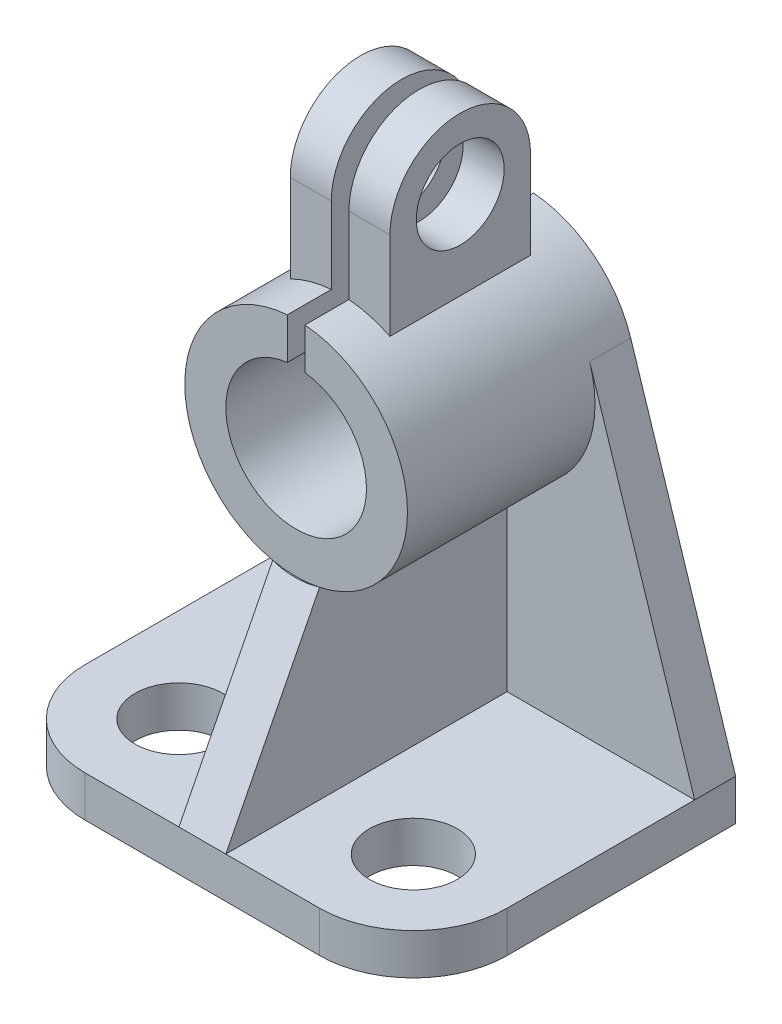
SolidWorks part; units mm, degrees
ref_plane "Front Plane" through (0, 0, 0) normal (0, 0, 1) x (1, 0, 0)
ref_plane "Top Plane" through (0, 0, 0) normal (0, 1, 0) x (1, 0, 0)
ref_plane "Right Plane" through (0, 0, 0) normal (1, 0, 0) x (0, 0, -1)
sketch "Sketch1" plane through (0, 0, 0) normal (0, 0, 1) x (1, 0, 0)
  line L0 (0, 0) -> (-33638.0787, 0) construction
  line L1 (0, 0) -> (0, 33638.0787) construction
  line L2 (-1.5, 68.9059) -> (-1.5, 75.9407)
  line L3 (36, 7) -> (-36, 7)
  line L4 (36, 7) -> (36, 0)
  line L5 (36, 0) -> (-36, 0)
  line L6 (-36, 7) -> (-36, 0)
  line L7 (0, 0) -> (0, 7) construction
  line L8 (36, 3.5) -> (-36, 3.5) construction
  line L9 (-4, 7) -> (4, 7)
  line L10 (-4, 7) -> (-4, 38.4258)
  line L12 (4, 7) -> (4, 38.4258)
  line L13 (1.5, 68.9059) -> (1.5, 75.9407)
  line L14 (36, 7) -> (18.0913, 62.8057)
  line L15 (-36, 7) -> (-18.0913, 62.8057)
  line L16 (-1.5, 101) -> (-8.5, 101)
  line L18 (1.5, 72.4233) -> (1.5, 101)
  line L19 (1.5, 101) -> (8.5, 101)
  line L20 (8.5, 73.9926) -> (8.5, 101)
  line L21 (-8.5, 73.9926) -> (-8.5, 101)
  line L23 (-1.5, 72.4233) -> (-1.5, 101)
  arc A0 (-1.5, 75.9407) -> (1.5, 75.9407) centre (0, 57) ccw
  arc A1 (-1.5, 68.9059) -> (1.5, 68.9059) centre (0, 57) ccw
  point P5 (0, 3.5)
  point P29 (0, 0)
  dimension "D4" = 50
  dimension "D5" = 38
  dimension "D6" = 24
  dimension "D1" = 72
  dimension "D2" = 7
  dimension "D3" = 8
  dimension "D7" = 3
  dimension "D8" = 44
  dimension "D9" = 7
extrude "Boss-Extrude1" add sketch "Sketch1" along normal blind 55 contours L3 L6 L5 L4 region at (0, 3.5, 0)
extrude "Boss-Extrude2" add sketch "Sketch1<3>" along normal blind 7 contours A0 L12 L3 L14 | A0 L15 L3 L10 region at (-17.7349, 25.0281, 0) region at (17.7349, 25.0281, 0)
sketch "Sketch1<3>" plane through (0, 0, 0) normal (0, 0, 1) x (1, 0, 0) same geometry as "Sketch1"
extrude "Boss-Extrude3" add sketch "Sketch1<4>" along normal blind 39 contours A1 L2 A0 L13 region at (0, 44.463, 0)
sketch "Sketch1<4>" plane through (0, 0, 0) normal (0, 0, 1) x (1, 0, 0) same geometry as "Sketch1"
extrude "Boss-Extrude4" add sketch "Sketch1<5>" along normal blind 24 from offset 7.5 contours A0 L20 L19 L18 | A0 L23 L16 L21 region at (-5.0437, 88.0986, 0) region at (5.0437, 88.0986, 0)
sketch "Sketch1<5>" plane through (0, 0, 0) normal (0, 0, 1) x (1, 0, 0) same geometry as "Sketch1"
extrude "Boss-Extrude5" add sketch "Sketch1<6>" along normal blind 55 contours A0 L10 L3 L12 region at (0, 22.5709, 0)
sketch "Sketch1<6>" plane through (0, 0, 0) normal (0, 0, 1) x (1, 0, 0) same geometry as "Sketch1"
fillet "Fillet3" 2 edges at (5, 101, 31.5) (5, 101, 7.5) type full round first side face at (5.0235, 88.0678, 31.5) second side face at (5.0235, 88.0678, 7.5) middle face at (5, 101, 19.5)
fillet "Fillet4" 2 edges at (-5, 101, 31.5) (-5, 101, 7.5) type full round first side face at (-5.0235, 88.0678, 31.5) second side face at (-5.0235, 88.0678, 7.5) middle face at (-5, 101, 19.5)
sketch "Sketch2" plane through (4, 0, 0) normal (1, 0, 0) x (0, 0, -1)
  line L0 (-39, 38.4258) -> (-55, 7)
  line L1 (-55, 7) -> (-55, 38.4258)
  line L2 (-55, 38.4258) -> (-39, 38.4258)
extrude "Cut-Extrude1" cut sketch "Sketch2" against normal blind 55
hole_wizard "Ø12.0mm Dowel Hole1" positions "3DSketch1" profile "Sketch3" hole size "Ø12.0" standard "ANSI Metric"
sketch3d "3DSketch1"
  line L0 (1.5, 89, 19.5) -> (8.5, 89, 19.5) construction
  point P0 (8.5, 89, 19.5)
sketch "Sketch3" plane through (8.5, 89, 19.5) normal (0, 1, 0) x (0, 0, -1)
  line L0 (0, 0) -> (0, 34.5065)
  line L1 (0, 34.5065) -> (7.5, 30)
  line L2 (7.5, 30) -> (7.5, 0)
  line L5 (7.5, 0) -> (0, 0)
  line L10 (0, 34.5065) -> (-7.5, 30) construction
  line L11 (0, -6.35) -> (0, 107.95) construction
  dimension "Hole Dia." = 15
  dimension "Hole Depth" = 30
  dimension "Drill Angle" = 118
fillet "Fillet5" radius 16 2 edges at (-36, 3.5, 55) (36, 3.5, 55)
hole_wizard "Ø12.0mm Dowel Hole2" positions "3DSketch2" profile "Sketch4" hole size "Ø12.0" standard "ANSI Metric"
sketch3d "3DSketch2"
  line L0 (20, 7, 39) -> (20, 0, 39) construction
  line L1 (-20, 0, 39) -> (-20, 7, 39) construction
  point P0 (20, 7, 39)
  point P4 (-20, 7, 39)
sketch "Sketch4" plane through (20, 7, 39) normal (1, 0, 0) x (0, 0, 1)
  line L0 (0, 0) -> (0, 34.5065)
  line L1 (0, 34.5065) -> (7.5, 30)
  line L2 (7.5, 30) -> (7.5, 0)
  line L5 (7.5, 0) -> (0, 0)
  line L10 (0, 34.5065) -> (-7.5, 30) construction
  line L11 (0, -6.35) -> (0, 107.95) construction
  dimension "Hole Dia." = 15
  dimension "Hole Depth" = 30
  dimension "Drill Angle" = 118
